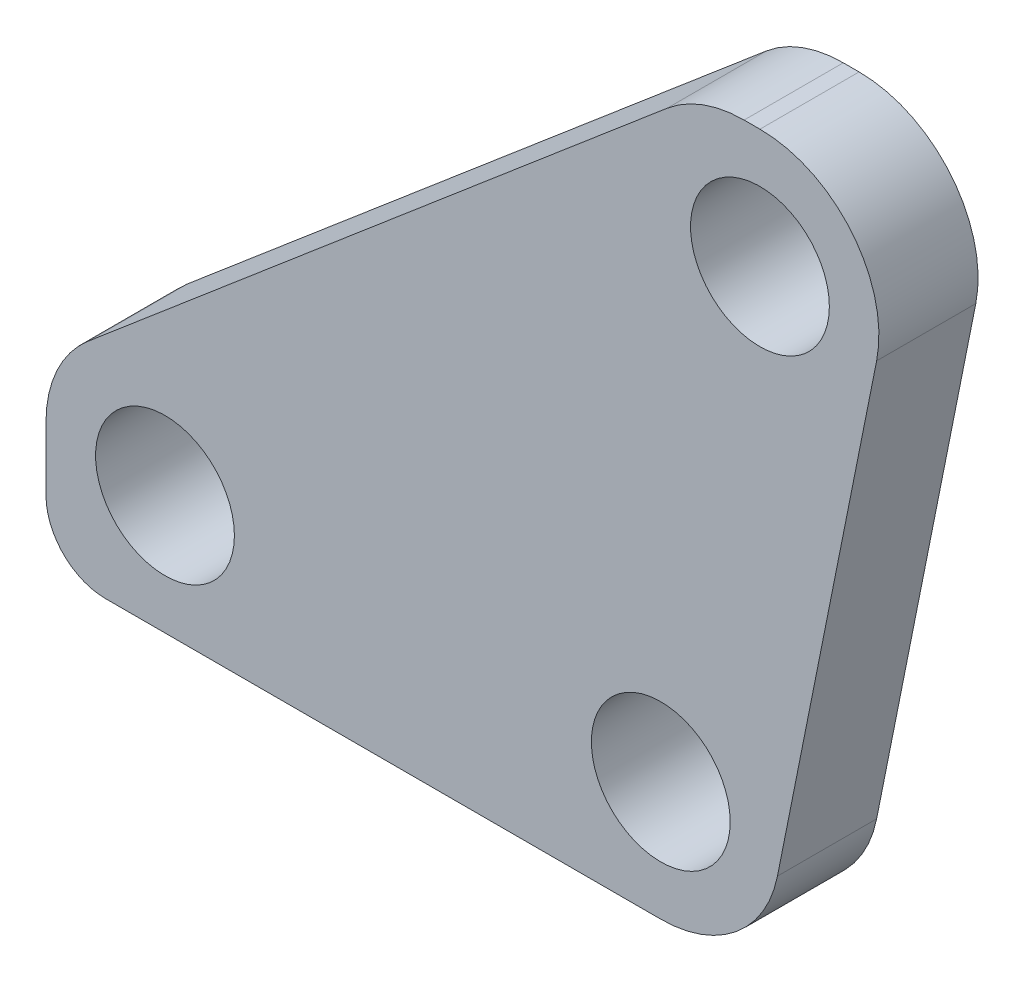
SolidWorks part; units mm, degrees
note: The reader was unsure of these and kept them because the rebuilt part matched: thickness of "Base-Flange1", "Sheet-Metal1".
ref_plane "Front Plane" through (0, 0, 0) normal (0, 0, 1) x (1, 0, 0)
ref_plane "Top Plane" through (0, 0, 0) normal (0, 1, 0) x (1, 0, 0)
ref_plane "Right Plane" through (0, 0, 0) normal (1, 0, 0) x (0, 0, -1)
sketch "Sketch1" plane through (0, 0, 0) normal (0, 0, 1) x (1, 0, 0)
  line L0 (-12.5, 0) -> (12.5, 0) construction
  line L1 (-15.5, -6) -> (12.5, -6)
  line L5 (18.3835, -1.1767) -> (23.3835, 23.8233)
  line L6 (-18.5, -3) -> (-18.5, 0.2222)
  line L7 (-16.3819, 4.7972) -> (12.8206, 29.5751)
  line L8 (16.7025, 31) -> (17.5, 31)
  line L9 (12.5, 0) -> (17.5, 25) construction
  line L10 (17.5, 25) -> (17.5, 31) construction
  circle A0 centre (17.5, 25) radius 3.5
  circle A1 centre (12.5, 0) radius 3.5
  circle A2 centre (-12.5, 0) radius 3.5
  arc A3 (17.5, 31) -> (23.3835, 23.8233) centre (17.5, 25) cw
  arc A4 (12.5, -6) -> (18.3835, -1.1767) centre (12.5, 0) ccw
  arc A5 (-18.5, 0.2222) -> (-16.3819, 4.7972) centre (-12.5, 0.2222) cw
  arc A6 (12.8206, 29.5751) -> (16.7025, 31) centre (16.7025, 25) cw
  arc A7 (-15.5, -6) -> (-18.5, -3) centre (-15.5, -3) cw
  point P12 (0, 0)
  point P26 (-18.5, 3)
  point P29 (14.5, 31)
  point P32 (-18.5, -6)
  dimension "D2" = 7
  dimension "D8" = 6
  dimension "D9" = 6
  dimension "D12" = 6
  dimension "D13" = 3
  dimension "D1" = 25
  dimension "D3" = 5
  dimension "D4" = 6
  dimension "D5" = 6
  dimension "D6" = 9
  dimension "D7" = 25
  dimension "D10" = 6
  dimension "D11" = 3
base flange "Base-Flange1" sketch "Sketch1" thickness 5 reverse thickness direction no parameters "D1"=0.7366
sketch "Bend-Lines1" [suppressed] plane through (0, 0, 0) normal (0, 1, 0) x (1, 0, 0)
sketch "Bounding-Box1" [suppressed] plane through (0, 0, 0) normal (0, 1, 0) x (1, 0, 0)
sheet metal parameters "Sheet-Metal1" thickness 5 parameters "D1"=0.7366
flat pattern "Flat-Pattern1" [suppressed]
sketch "Bend-Lines2" plane through (0, 0, 0) normal (0, 1, 0) x (1, 0, 0)
sketch3d "Bounding-Box2" [suppressed]
  line L0 (16, -16, 0) -> (16, 16, 0) construction
  line L1 (-16, -16, 0) -> (-16, 16, 0) construction
  line L2 (16, -16, 0) -> (-16, -16, 0) construction
  line L3 (16, 16, 0) -> (-16, 16, 0) construction
